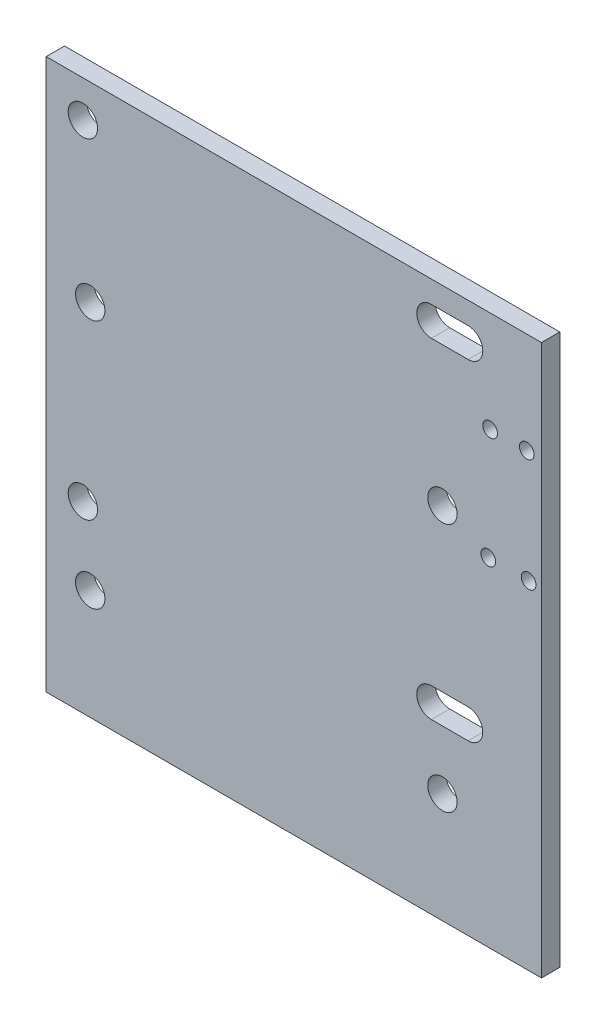
SolidWorks part; units mm, degrees
ref_plane "Front" through (0, 0, 0) normal (0, 0, 1) x (1, 0, 0)
ref_plane "Top" through (0, 0, 0) normal (0, 1, 0) x (1, 0, 0)
ref_plane "Right" through (0, 0, 0) normal (1, 0, 0) x (0, 0, -1)
sketch "Sketch1" plane through (0, 0, 0) normal (0, 0, 1) x (1, 0, 0)
  line L1 (-67.5, 75) -> (67.5, 75)
  line L2 (-67.5, 75) -> (-67.5, -75)
  line L3 (-67.5, -75) -> (67.5, -75)
  line L4 (67.5, 75) -> (67.5, -75)
  line L5 (-67.5, 75) -> (67.5, -75) construction
  line L6 (-67.5, -75) -> (67.5, 75) construction
  point P0 (0, 0)
  dimension "D1" = 135
  dimension "D2" = 150
extrude "Boss-Extrude1" add sketch "Sketch1" along normal blind 5
sketch "Sketch2" plane through (0, 0, 5) normal (0, 0, 1) x (1, 0, 0)
  line L0 (67.5, 75) -> (-67.5, 75) construction
  line L1 (-67.5, 75) -> (-67.5, -75) construction
  line L2 (-114.5449, 20) -> (116.0349, 20) construction
  line L3 (37.5, 65) -> (47.5, 65) construction
  line L4 (37.5, 69) -> (47.5, 69)
  line L5 (37.5, 61) -> (47.5, 61)
  line L7 (37.5, -25) -> (47.5, -25) construction
  line L8 (37.5, -29) -> (47.5, -29)
  line L9 (37.5, -21) -> (47.5, -21)
  circle A0 centre (-57.5, 65) radius 4
  arc A1 (37.5, 69) -> (37.5, 61) centre (37.5, 65) ccw
  arc A2 (37.5, -29) -> (37.5, -21) centre (37.5, -25) cw
  circle A3 centre (-57.5, -25) radius 4
  arc A4 (47.5, 61) -> (47.5, 69) centre (47.5, 65) ccw
  arc A5 (47.5, -21) -> (47.5, -29) centre (47.5, -25) cw
  point P14 (42.5, 65)
  point P21 (42.5, -25)
  dimension "D1" = 8
  dimension "D2" = 10
  dimension "D3" = 10
  dimension "D4" = 4
  dimension "D6" = 10
  dimension "D5" = 45
  dimension "D7" = 110
extrude "Cut-Extrude1" cut sketch "Sketch2" against normal up to next
sketch "Sketch4" plane through (0, 0, 5) normal (0, 0, 1) x (1, 0, 0)
  circle A0 centre (44.55, 40.25) radius 2.35
  circle A1 centre (16.45, 40.25) radius 2.35
  circle A2 centre (-33.45, 40.25) radius 2.35
  circle A3 centre (-61.55, 40.25) radius 2.35
  circle A4 centre (-61.55, -62.75) radius 2.35
  circle A5 centre (-33.45, -62.75) radius 2.35
  circle A6 centre (44.55, -62.75) radius 2.35
  circle A7 centre (16.45, -62.75) radius 2.35
extrude "Cut-Extrude3" [suppressed] cut sketch "Sketch4" against normal through all
sketch "Sketch6" plane through (0, 0, 5) normal (0, 0, 1) x (1, 0, 0)
  line L1 (-67.5, 75) -> (-67.5, -75) construction
  circle A0 centre (-55.5, 23) radius 4
  circle A1 centre (-55.5, -45) radius 4
  circle A2 centre (40.5, 23) radius 4
  circle A3 centre (40.5, -45) radius 4
  circle A10 centre (-57.5, -25) radius 4 construction
  dimension "D1" = 8
  dimension "D2" = 8
  dimension "D3" = 8
  dimension "D4" = 8
  dimension "D8" = 68
  dimension "D9" = 20
  dimension "D5" = 96
  dimension "D6" = 96
  dimension "D7" = 12
extrude "Cut-Extrude5" cut sketch "Sketch6" against normal up to next
sketch "Sketch7" plane through (0, 0, 0) normal (0, 0, -1) x (-1, 0, 0)
  line L1 (-37.5, 69) -> (-47.5, 69) construction
  circle A0 centre (-63.5, 47.5) radius 2
  circle A1 centre (-53.5, 47.5) radius 2
  circle A2 centre (-64, 17) radius 2
  circle A3 centre (-53, 17) radius 2
  dimension "D1" = 4
  dimension "D2" = 4
  dimension "D3" = 4
  dimension "D4" = 4
extrude "Cut-Extrude6" cut sketch "Sketch7" against normal up to next
